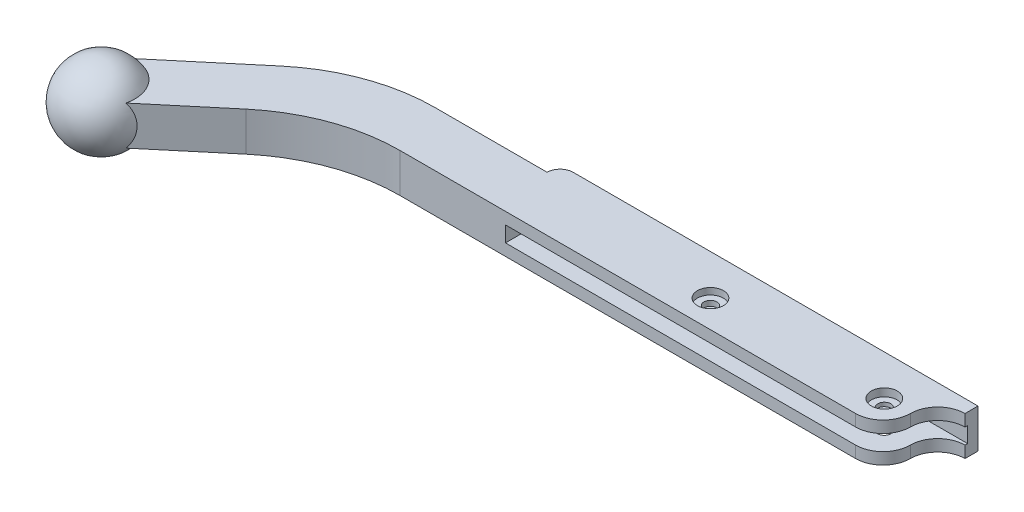
SolidWorks part; units mm, degrees
ref_plane "前视基准面" through (0, 0, 0) normal (0, 0, 1) x (1, 0, 0)
ref_plane "上视基准面" through (0, 0, 0) normal (0, 1, 0) x (1, 0, 0)
ref_plane "右视基准面" through (0, 0, 0) normal (1, 0, 0) x (0, 0, -1)
sketch "草图1" plane through (0, 0, 0) normal (0, 1, 0) x (1, 0, 0)
  line L1 (-107.5292, 13.1553) -> (42.4708, 13.1553)
  line L2 (-107.5292, 13.1553) -> (-107.5292, -7.8447)
  line L3 (-107.5292, -7.8447) -> (42.4708, -7.8447)
  line L4 (42.4708, 13.1553) -> (42.4708, -7.8447)
  dimension "D1" = 150
  dimension "D2" = 21
extrude "凸台-拉伸1" add sketch "草图1" along normal blind 15
sketch "草图2" plane through (42.4708, 0, 0) normal (1, 0, 0) x (0, 0, -1)
  line L0 (-7.8447, 15) -> (-7.8447, 0) construction
  line L1 (-7.8447, 10.5) -> (13.1553, 10.5)
  line L2 (-7.8447, 10.5) -> (-7.8447, 4.5)
  line L3 (-7.8447, 4.5) -> (13.1553, 4.5)
  line L4 (13.1553, 10.5) -> (13.1553, 4.5)
  line L5 (13.1553, 15) -> (13.1553, 0) construction
  line L6 (-7.8447, 15) -> (13.1553, 15) construction
  line L7 (-7.8447, 0) -> (13.1553, 0) construction
  dimension "D1" = 4.5
  dimension "D2" = 4.5
extrude "切除-拉伸1" cut sketch "草图2" against normal blind 145
sketch "草图3" plane through (0, 15, 0) normal (0, 1, 0) x (1, 0, 0)
  line L0 (42.4708, -7.8447) -> (42.4708, 13.1553) construction
  line L1 (42.4708, 13.1553) -> (-107.5292, 13.1553) construction
  circle A0 centre (32.4708, 2.6553) radius 5
  dimension "D1" = 10
  dimension "D2" = 10.5
extrude "切除-拉伸2" cut sketch "草图3" against normal blind 3
sketch "草图4" plane through (0, 0, 0) normal (0, -1, 0) x (-1, 0, 0)
  line L0 (-42.4708, -7.8447) -> (-42.4708, 13.1553) construction
  line L1 (107.5292, -7.8447) -> (-42.4708, -7.8447) construction
  circle A0 centre (-32.4708, 2.6553) radius 5
  dimension "D1" = 10
  dimension "D2" = 10.5
extrude "切除-拉伸3" cut sketch "草图4" against normal blind 3
sketch "草图5" plane through (0, 3, 0) normal (0, -1, 0) x (-1, 0, 0)
  circle A0 centre (-32.4708, 2.6553) radius 2.5
  circle A1 centre (-32.4708, 2.6553) radius 5 construction
  dimension "D1" = 0
extrude "切除-拉伸4" cut sketch "草图5" against normal blind 20
sketch "草图6" plane through (0, 15, 0) normal (0, 1, 0) x (1, 0, 0)
  line L0 (42.4708, 13.1553) -> (-107.5292, 13.1553) construction
  circle A0 centre (-34.2955, 2.6553) radius 5
  circle A1 centre (32.4708, 2.6553) radius 2.5 construction
  dimension "D1" = 10.5
  dimension "D2" = 66.7663
extrude "切除-拉伸5" cut sketch "草图6" against normal blind 20
sketch "草图7" plane through (0, 4.5, 0) normal (0, 1, 0) x (1, 0, 0)
  circle A0 centre (-34.2955, 2.6553) radius 6
  circle A2 centre (-34.2955, 2.6553) radius 5 construction
  dimension "D1" = 0
extrude "凸台-拉伸2" add sketch "草图7" against normal blind 2
sketch "草图8" plane through (0, 10.5, 0) normal (0, -1, 0) x (-1, 0, 0)
  circle A0 centre (34.2955, 2.6553) radius 6
  circle A1 centre (34.2955, 2.6553) radius 5 construction
  dimension "D1" = 0
extrude "凸台-拉伸3" add sketch "草图8" against normal blind 2
sketch "草图9" plane through (0, 12.5, 0) normal (0, 1, 0) x (1, 0, 0)
  circle A0 centre (-34.2955, 2.6553) radius 2.5
  circle A2 centre (-34.2955, 2.6553) radius 5 construction
  dimension "D1" = 0
extrude "切除-拉伸6" cut sketch "草图9" against normal blind 20
sketch "草图12" plane through (0, 15, 0) normal (0, 1, 0) x (1, 0, 0)
  line L0 (-107.5292, -7.8447) -> (-167.5292, -7.8447)
  line L1 (-167.5292, -7.8447) -> (-217.3221, -49.6259)
  line L2 (-107.5292, 13.1553) -> (-175.1726, 13.1553)
  line L3 (-217.3221, -49.6259) -> (-230.8206, -33.539)
  line L4 (-230.8206, -33.539) -> (-175.1726, 13.1553)
  line L5 (-107.5292, 13.1553) -> (-107.5292, -7.8447)
  dimension "D1" = 60
  dimension "D2" = 140
  dimension "D3" = 21
  dimension "D4" = 90
  dimension "D5" = 65
extrude "凸台-拉伸5" add sketch "草图12" against normal blind 15 separate body
sketch "草图13" plane through (-151.9658, 0, 127.5145) normal (-0.766, 0, 0.6428) x (0.6428, 0, 0.766)
  line L0 (-122.6763, 7.5) -> (-101.6763, 7.5) construction
  line L1 (-122.6763, 0) -> (-122.6763, 15) construction
  line L2 (-101.6763, 0) -> (-101.6763, 15) construction
  line L3 (-112.1763, 15) -> (-112.1763, 7.5) construction
  line L4 (-122.6763, 15) -> (-101.6763, 15) construction
  line L5 (-112.1763, 7.5) -> (-112.1763, 0) construction
  line L6 (-122.6763, 0) -> (-101.6763, 0) construction
  line L7 (-112.1763, 22.5) -> (-112.1763, -7.5)
  arc A0 (-112.1763, -7.5) -> (-112.1763, 22.5) centre (-112.1763, 7.5) ccw
revolve "旋转3" add sketch "草图13" angle 360 about L7
sketch "草图14" plane through (0, 0, -13.1553) normal (0, 0, -1) x (-1, 0, 0)
  line L1 (107.5292, 15) -> (-52.9708, 15)
  line L2 (107.5292, 15) -> (107.5292, 0)
  line L3 (107.5292, 0) -> (-52.9708, 0)
  line L4 (-52.9708, 15) -> (-52.9708, 0)
  dimension "D1" = 160.5
extrude "凸台-拉伸6" add sketch "草图14" along normal blind 5
fillet "圆角1" radius 5 1 edges at (-107.5292, 7.5, -18.1553)
fillet "圆角2" radius 10.5 4 edges at (42.4708, 2.25, 7.8447) (42.4708, 2.25, -13.1553) (42.4708, 12.75, 7.8447) (42.4708, 12.75, -13.1553)
fillet "圆角3" radius 67.5 2 edges at (-167.5292, 7.5, 7.8447) (-175.1726, 7.5, -13.1553)
sketch "草图15" plane through (0, 10.5, 0) normal (0, -1, 0) x (-1, 0, 0)
  point P0 (-32.4708, 2.6553)
ref_point "点2"
sketch "草图17" plane through (-102.5292, 0, 0) normal (1, 0, 0) x (0, 0, -1)
  line L0 (13.1553, 10.5) -> (13.1553, 4.5) construction
  line L1 (-7.8447, 10.5) -> (14.1553, 10.5)
  line L2 (-7.8447, 10.5) -> (-7.8447, 4.5)
  line L3 (-7.8447, 4.5) -> (14.1553, 4.5)
  line L4 (14.1553, 10.5) -> (14.1553, 4.5)
  dimension "D1" = 1
extrude "切除-拉伸7" cut sketch "草图17" along normal blind 200
